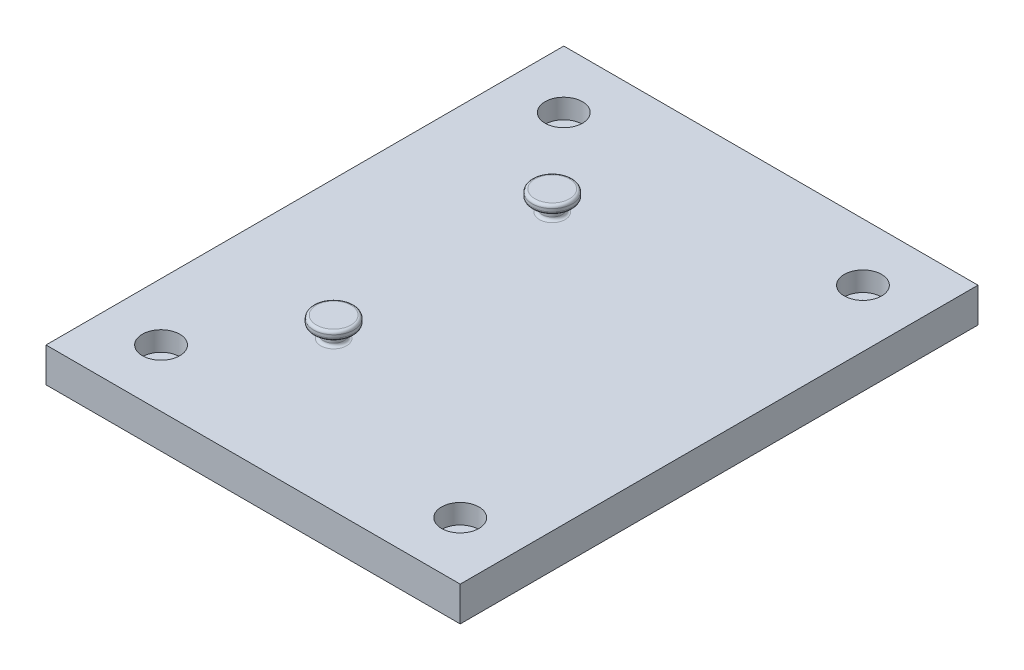
SolidWorks part; units mm, degrees
ref_plane "Front Plane" through (0, 0, 0) normal (0, 0, 1) x (1, 0, 0)
ref_plane "Top Plane" through (0, 0, 0) normal (0, 1, 0) x (1, 0, 0)
ref_plane "Right Plane" through (0, 0, 0) normal (1, 0, 0) x (0, 0, -1)
sketch "Szkic1" plane through (0, 0, 0) normal (0, 1, 0) x (1, 0, 0)
  line L0 (36, 45) -> (-36, -45) construction
  line L1 (-36, 45) -> (36, 45)
  line L2 (-36, 45) -> (-36, -45)
  line L3 (-36, -45) -> (36, -45)
  line L4 (36, 45) -> (36, -45)
  dimension "D1" = 72
  dimension "D2" = 90
extrude "Dodanie-wyciągnięcie1" add sketch "Szkic1" along normal blind 6
sketch "Szkic2" plane through (0, 6, 0) normal (0, 1, 0) x (1, 0, 0)
  line L0 (-36, 45) -> (-36, -45) construction
  line L1 (36, 45) -> (-36, 45) construction
  line L3 (-12, 19) -> (-12, 45) construction
  line L4 (-12, -19) -> (-12, -45) construction
  line L5 (-36, -45) -> (36, -45) construction
  circle A0 centre (-12, -19) radius 1.75
  circle A1 centre (-12, 19) radius 1.75
  circle A2 centre (-12, 19) radius 3.5
  circle A3 centre (-12, -19) radius 3.5
  dimension "D3" = 3.5
  dimension "D4" = 3.5
  dimension "D5" = 7
  dimension "D6" = 7
  dimension "D1" = 38
  dimension "D2" = 24
extrude "Dodanie-wyciągnięcie2" add sketch "Szkic2" along normal blind 2 contours A0 | A1 region at (-12, 6, 19) region at (-12, 6, -19)
extrude "Dodanie-wyciągnięcie3" add sketch "Szkic2<5>" along normal blind 1.5 from surface contours A3 | A2 starting at face at (-12, 8, 20.75)
sketch "Szkic2<5>" plane through (0, 6, 0) normal (0, 1, 0) x (1, 0, 0) same geometry as "Szkic2"
fillet "Zaokrąglenie1" radius 0.5 8 edges at (-12, 9.5, -15.5) (-12, 8, -15.5) (-12, 9.5, 22.5) (-12, 8, 22.5) (-12, 6, -17.25) (-12, 6, 20.75) (-12, 8, -17.25) (-12, 8, 20.75)
hole_wizard "CBORE for M3 Hex Socket Head Cap Screw1" positions "Szkic3" profile "Szkic4" counterbore size "M3" standard "DIN"
sketch "Szkic3" plane through (0, 6, 0) normal (0, 1, 0) x (1, 0, 0)
  line L0 (-26, 35) -> (-26, -35) construction
  line L2 (-26, 35) -> (26, 35) construction
  line L3 (26, 35) -> (26, -35) construction
  line L4 (26, -35) -> (-26, -35) construction
  line L6 (-36, 45) -> (-36, -45) construction
  line L7 (36, 45) -> (-36, 45) construction
  line L8 (-36, -45) -> (36, -45) construction
  line L10 (36, -45) -> (36, 45) construction
  point P0 (-26, 35)
  point P2 (26, 35)
  point P4 (26, -35)
  point P6 (-26, -35)
  dimension "D1" = 10
  dimension "D2" = 10
  dimension "D3" = 10
  dimension "D4" = 10
sketch "Szkic4" plane through (-26, 6, -35) normal (1, 0, 0) x (0, 0, 1)
  line L0 (0, 0) -> (0, 8.6614)
  line L1 (0, 8.6614) -> (1.6, 7.7)
  line L2 (1.6, 7.7) -> (1.6, 3.4)
  line L3 (1.6, 3.4) -> (3.25, 3.4)
  line L4 (3.25, 3.4) -> (3.25, 0)
  line L5 (3.25, 0) -> (0, 0)
  line L10 (0, 8.6614) -> (-1.6, 7.7) construction
  line L11 (0, -6.35) -> (0, 107.95) construction
  dimension "Hole Dia." = 3.2
  dimension "Hole Depth" = 7.7
  dimension "C'Bore Dia." = 6.5
  dimension "C'Bore Depth" = 3.4
  dimension "Drill Angle" = 118
